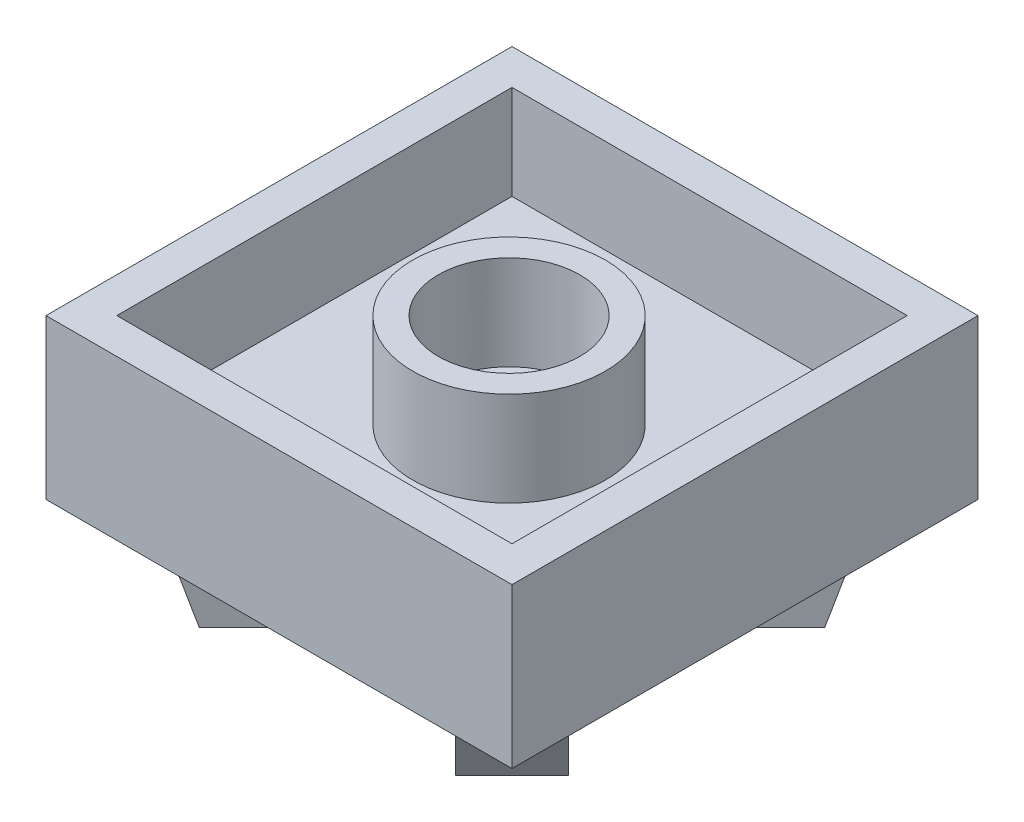
SolidWorks part; units mm, degrees
ref_plane "Front Plane" through (0, 0, 0) normal (0, 0, 1) x (1, 0, 0)
ref_plane "Top Plane" through (0, 0, 0) normal (0, 1, 0) x (1, 0, 0)
ref_plane "Right Plane" through (0, 0, 0) normal (1, 0, 0) x (0, 0, -1)
sketch "Sketch2" plane through (0, 0, 0) normal (0, 1, 0) x (1, 0, 0)
  line L1 (0, 0) -> (15.8, 0)
  line L2 (0, 0) -> (0, 15.8)
  line L3 (0, 15.8) -> (15.8, 15.8)
  line L4 (15.8, 0) -> (15.8, 15.8)
  dimension "D1" = 15.8
  dimension "D2" = 15.8
extrude "Boss-Extrude2" add sketch "Sketch2" against normal blind 5.4
sketch "Sketch4" plane through (0, 0, 0) normal (0, 1, 0) x (1, 0, 0)
  line L0 (15.8, 0) -> (15.8, 15.8) construction
  line L1 (14.6, 14.6) -> (1.2, 14.6)
  line L2 (14.6, 14.6) -> (14.6, 1.2)
  line L3 (14.6, 1.2) -> (1.2, 1.2)
  line L4 (1.2, 14.6) -> (1.2, 1.2)
  line L5 (0, -55) -> (0, 55) construction
  line L6 (-55, 0) -> (55, 0) construction
  line L7 (15.8, 15.8) -> (0, 15.8) construction
  dimension "D1" = 1.2
  dimension "D2" = 1.2
  dimension "D3" = 1.2
  dimension "D4" = 1.2
extrude "Cut-Extrude1" cut sketch "Sketch4" against normal offset from surface (3.2 mm away) 2.2 up to face at (7.9, -5.4, -7.9)
sketch "Sketch7" plane through (0, -3.2, 0) normal (0, 1, 0) x (1, 0, 0)
  line L0 (15.8, 0) -> (15.8, 15.8) construction
  line L1 (15.8, 15.8) -> (0, 15.8) construction
  circle A0 centre (7.85, 7.85) radius 3.265
  circle A1 centre (7.85, 7.85) radius 2.4
  dimension "D1" = 6.53
  dimension "D2" = 4.8
  dimension "D3" = 7.95
  dimension "D4" = 7.95
extrude "Boss-Extrude5" add sketch "Sketch7" along normal up to surface (3.2 mm away) up to face at (7.9, 0, -7.9)
sketch "Sketch8" plane through (0, -5.4, 0) normal (0, -1, 0) x (-1, 0, 0)
  line L0 (-15.8, 0) -> (-15.8, 15.8) construction
  line L1 (-15.8, 15.8) -> (0, 15.8) construction
  circle A0 centre (-7.9, 7.9) radius 5.15
  dimension "D1" = 10.3
  dimension "D2" = 7.9
  dimension "D3" = 7.9
extrude "Cut-Extrude2" cut sketch "Sketch8" against normal blind 0.3
sketch "Sketch11" plane through (0, -5.4, 0) normal (0, -1, 0) x (1, 0, 0)
  line L2 (7.9, -7.9) -> (15.8, 0)
  line L3 (4.51, 0) -> (-4.51, 0) construction
  line L4 (11.683, -2.2078) -> (13.5922, -4.117)
  line L5 (13.5922, -4.117) -> (11.683, -2.2078)
  line L6 (13.5922, -4.117) -> (14.1579, -3.5513)
  line L7 (11.683, -2.2078) -> (12.2487, -1.6421)
  line L8 (14.1579, -3.5513) -> (12.2487, -1.6421)
  line L9 (11.683, -2.2078) -> (10.4597, -3.4311)
  line L10 (13.5922, -4.117) -> (12.3689, -5.3403)
  circle A0 centre (7.9, -7.9) radius 6.7
  circle A1 centre (7.9, -7.9) radius 5.15 construction
  point P9 (12.6376, -3.1624)
  circle M6 centre (7.9, -7.9) radius 5.15
  dimension "D1" = 13.4
  dimension "D2" = 2.7
  dimension "D3" = 0.8
extrude "Boss-Extrude8" add sketch "Sketch11" along normal blind 2.8 contours L2 L8 L7 L4 | A0 L4 L9 | L2 A0 L9 M6 | L10 A0 L2 M6 | A0 L10 L4 | L6 L8 L2 L4 region at (11.5727, -5.4, -3.2684) region at (12.5316, -5.4, -4.2273) region at (12.4432, -5.4, -2.4022) region at (11.8921, -5.4, -2.475) region at (13.3978, -5.4, -3.3568) region at (13.325, -5.4, -3.9079)
ref_axis "Axis1" through (7.9, -5.1, -7.9) along (0, -1, 0)
sketch "Sketch29" plane through (6.9454, 0, -6.9454) normal (-0.7071, 0, 0.7071) x (0.7071, 0, 0.7071)
  line L0 (7.5, -8.2) -> (7.5, -5.4)
  line L1 (7.5, -5.4) -> (8.4, -5.4)
  line L2 (8.4, -5.4) -> (7.5, -8.2)
  dimension "D1" = 0.9
extrude "Boss-Extrude11" add sketch "Sketch29" against normal up to vertex up to point (14.1579, -5.4, -3.5513)
pattern_circular "CirPattern1" count 4 over 360 about axis through (7.9, -5.1, -7.9) along (0, -1, 0) of "Boss-Extrude8", "Boss-Extrude11"
